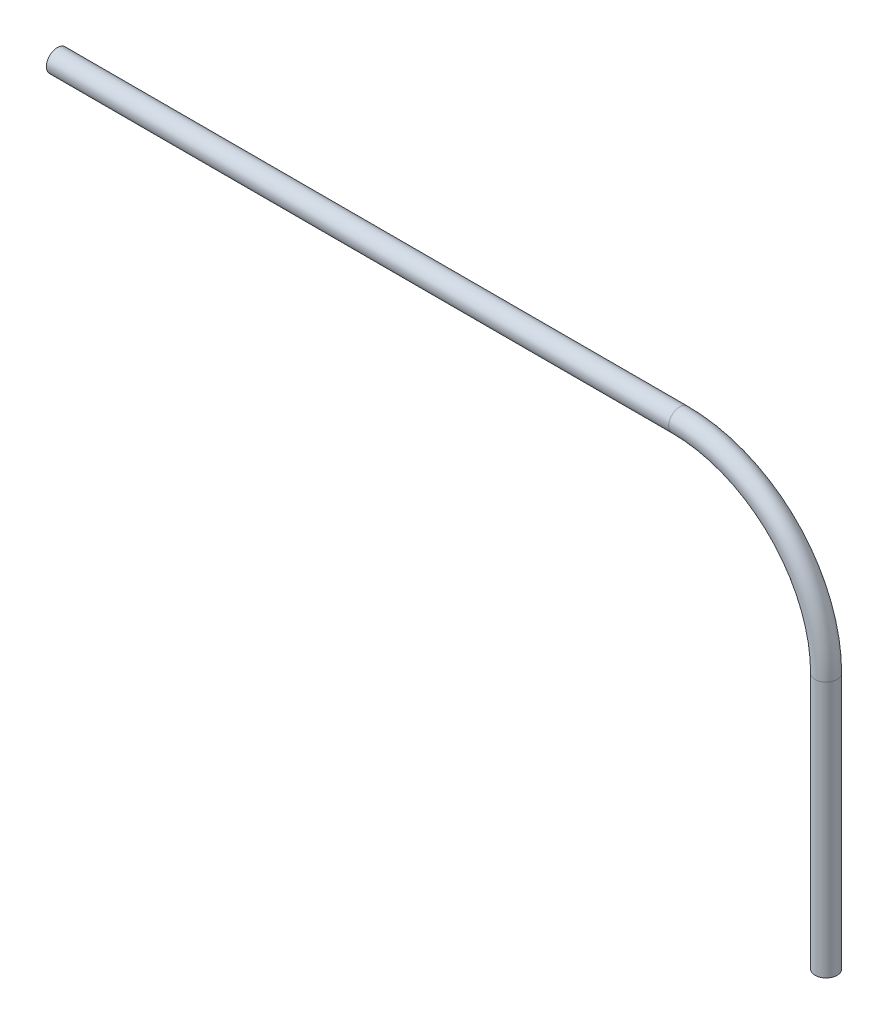
SolidWorks part; units mm, degrees
ref_plane "Front Plane" through (0, 0, 0) normal (0, 0, 1) x (1, 0, 0)
ref_plane "Top Plane" through (0, 0, 0) normal (0, 1, 0) x (1, 0, 0)
ref_plane "Right Plane" through (0, 0, 0) normal (1, 0, 0) x (0, 0, -1)
sketch "Sketch1" plane through (0, 0, 0) normal (0, 0, 1) x (1, 0, 0)
  line L0 (4624.9602, -100) -> (4624.9602, 600)
  line L1 (4224.9602, 1000) -> (2524.9602, 1000)
  arc A0 (4624.9602, 600) -> (4224.9602, 1000) centre (4224.9602, 600) ccw
  point P2 (4711.9167, 1977.1333)
  point P6 (4624.9602, 1000)
  point P7 (4624.9602, 0)
  dimension "D3" = 400
  dimension "D1" = 1700
  dimension "D2" = 700
sweep "Sweep-Thin1" add path "Sketch1" circular profile diameter 60 parameters "D1"=3, "D3"=60
